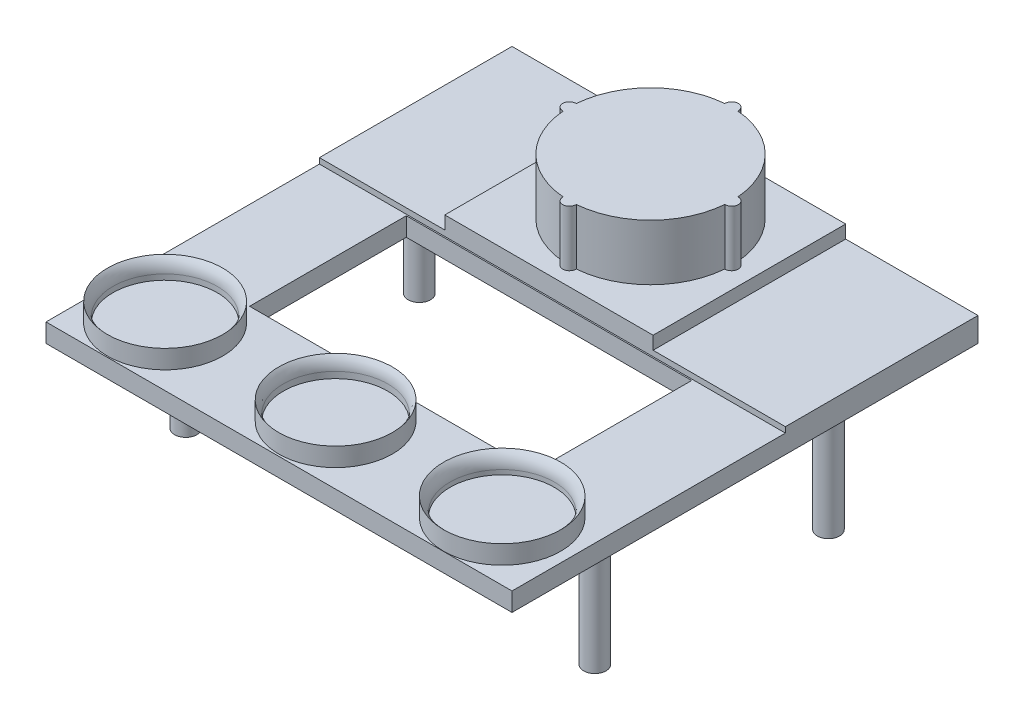
SolidWorks part; units mm, degrees
ref_plane "前视基准面" through (0, 0, 0) normal (0, 0, 1) x (1, 0, 0)
ref_plane "上视基准面" through (0, 0, 0) normal (0, 1, 0) x (1, 0, 0)
ref_plane "右视基准面" through (0, 0, 0) normal (1, 0, 0) x (0, 0, -1)
sketch "草图3" plane through (0, 0, 0) normal (0, 1, 0) x (1, 0, 0)
  line L1 (0, 0) -> (250, 0)
  line L2 (0, 0) -> (0, -250)
  line L3 (0, -250) -> (250, -250)
  line L4 (250, 0) -> (250, -250)
  line L5 (47.3311, -104.0234) -> (200.4102, -104.0234)
  line L6 (47.3311, -104.0234) -> (47.3311, -188.1224)
  line L7 (47.3311, -188.1224) -> (200.4102, -188.1224)
  line L8 (200.4102, -104.0234) -> (200.4102, -188.1224)
  dimension "D1" = 250
  dimension "D2" = 250
extrude "凸台-拉伸3" add sketch "草图3" along normal blind 10
sketch "草图4" plane through (0, 0, 0) normal (0, 1, 0) x (1, 0, 0)
  line L0 (250, 0) -> (0, 0) construction
  line L1 (0, -250) -> (250, -250) construction
  circle A0 centre (11.9091, -61.6017) radius 6
  circle A1 centre (231.3649, -61.6017) radius 6
  circle A2 centre (231.3649, -186.9353) radius 6
  circle A3 centre (11.9091, -186.9353) radius 6
  point P0 (75, 0)
  point P1 (175, 0)
  point P4 (75, -250)
  point P5 (175, -250)
  point P8 (75, -50)
  point P13 (175, -50)
  point P14 (75, -200)
  point P15 (175, -200)
  dimension "D1" = 75
  dimension "D2" = 75
  dimension "D3" = 75
  dimension "D4" = 75
  dimension "D5" = 50
  dimension "D6" = 50
extrude "凸台-拉伸4" add sketch "草图4" against normal blind 65
sketch "草图5" plane through (0, 10, 0) normal (0, 1, 0) x (1, 0, 0)
  circle A0 centre (32.3748, -218.4719) radius 28
  circle A1 centre (123.8147, -218.4719) radius 28
  circle A2 centre (213.2226, -218.4719) radius 28
  circle A3 centre (32.3748, -218.4719) radius 30.9208
  circle A4 centre (123.8147, -218.4719) radius 30.5063
  circle A5 centre (213.2226, -218.4719) radius 31.4231
extrude "凸台-拉伸5" add sketch "草图5" along normal blind 10
fillet "圆角1" radius 10 3 edges at (213.2226, 20, 246.4719) (123.8147, 20, 246.4719) (32.3748, 20, 246.4719)
sketch "草图6" plane through (0, 10, 0) normal (0, 1, 0) x (1, 0, 0)
  line L0 (250, -250) -> (250, 0) construction
  line L1 (0, 0) -> (250, 0)
  line L2 (0, 0) -> (0, -103.3254)
  line L3 (0, -103.3254) -> (250, -103.3254)
  line L4 (250, 0) -> (250, -103.3254)
extrude "凸台-拉伸6" add sketch "草图6" along normal blind 3
sketch "草图7" plane through (0, 0, 0) normal (0, 1, 0) x (1, 0, 0)
  line L0 (250, 0) -> (0, 0) construction
  line L1 (67.2574, 0) -> (179.0173, 0)
  line L2 (67.2574, 0) -> (67.2574, -103.3254)
  line L3 (67.2574, -103.3254) -> (179.0173, -103.3254)
  line L4 (179.0173, 0) -> (179.0173, -103.3254)
  line L5 (0, -103.3254) -> (250, -103.3254) construction
extrude "凸台-拉伸7" add sketch "草图7" along normal blind 20
ref_plane "基准面4" through (0, 20, 0) normal (0, 1, 0) x (1, 0, 0)
sketch "草图8" plane through (0, 20, 0) normal (0, 1, 0) x (1, 0, 0)
  arc A0 (80.7698, -53.362) -> (120.601, -93.1933) centre (124.1358, -49.8272) ccw
  arc A1 (80.7698, -46.2924) -> (80.7698, -53.362) centre (80.626, -49.8272) ccw
  arc A2 (127.6706, -6.4612) -> (120.601, -6.4612) centre (124.1358, -6.3174) ccw
  arc A3 (167.5019, -53.362) -> (167.5019, -46.2924) centre (167.6457, -49.8272) ccw
  arc A4 (120.601, -93.1933) -> (127.6706, -93.1933) centre (124.1358, -93.3371) ccw
  arc A5 (127.6706, -93.1933) -> (167.5019, -53.362) centre (124.1358, -49.8272) ccw
  arc A6 (167.5019, -46.2924) -> (127.6706, -6.4612) centre (124.1358, -49.8272) ccw
  arc A7 (120.601, -6.4612) -> (80.7698, -46.2924) centre (124.1358, -49.8272) ccw
extrude "凸台-拉伸8" add sketch "草图8" along normal blind 30
